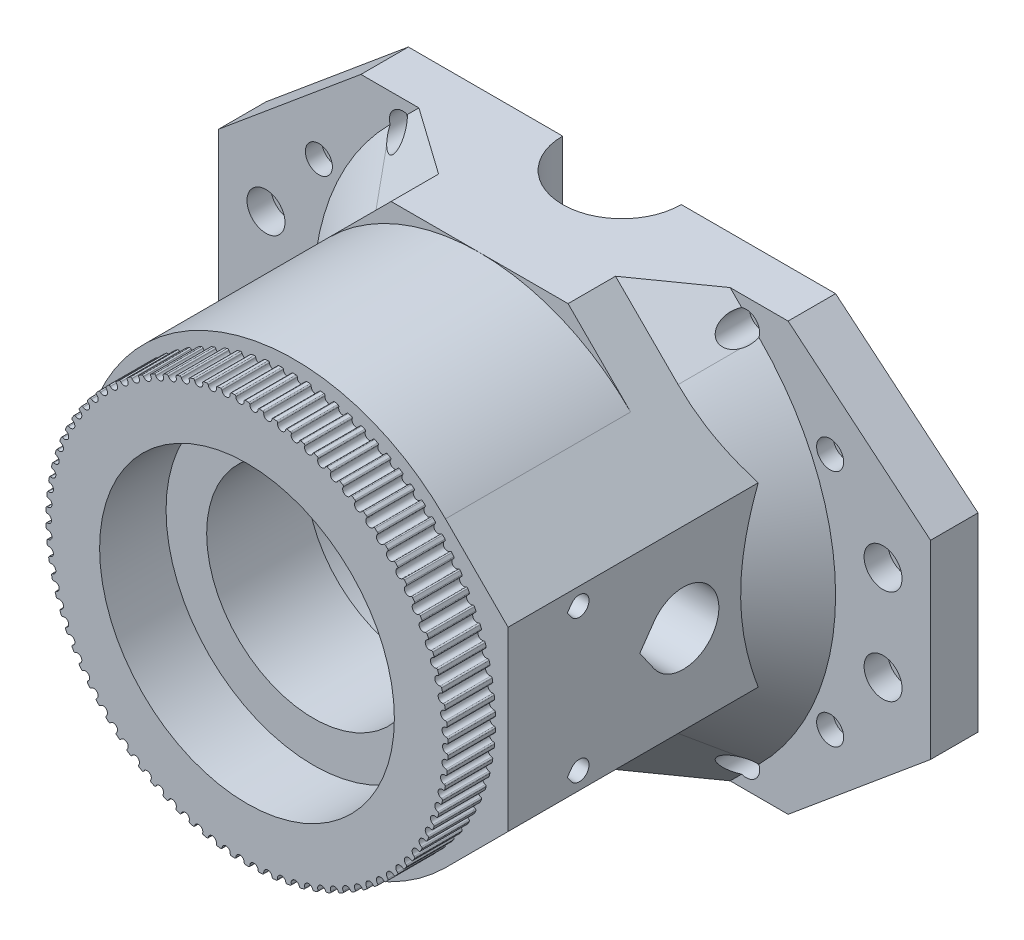
SolidWorks part; units mm, degrees
ref_plane "Front Plane" through (0, 0, 0) normal (1, 0, 0) x (0, 1, 0)
ref_plane "Top Plane" through (0, 0, 0) normal (0, 0, 1) x (0, 1, 0)
ref_plane "Right Plane" through (0, 0, 0) normal (0, 1, 0) x (-1, 0, 0)
sketch "Sketch1" plane through (0, 0, 0) normal (1, 0, 0) x (0, 1, 0)
  line L0 (-45, -80) -> (45, -80)
  line L1 (-31, 0) -> (31, 0)
  line L2 (-31, 0) -> (-31, -14)
  line L3 (-31, -14) -> (31, -14)
  line L4 (31, 0) -> (31, -14)
  line L5 (-31, 0) -> (31, -14) construction
  line L6 (-31, -14) -> (31, 0) construction
  line L7 (-31, -36) -> (31, -36)
  line L8 (-31, -36) -> (-31, -50)
  line L9 (-31, -50) -> (31, -50)
  line L10 (31, -36) -> (31, -50)
  line L11 (-31, -36) -> (31, -50) construction
  line L12 (-31, -50) -> (31, -36) construction
  line L13 (45, -80) -> (45, -1)
  line L14 (45, -1) -> (31, -1)
  line L15 (-31, -1) -> (-45, -1)
  line L16 (-45, -1) -> (-45, -80)
  point P0 (0, -7)
  point P5 (0, -43)
  point P16 (0, 0)
  dimension "D1" = 62
  dimension "D2" = 62
  dimension "D3" = 14
  dimension "D4" = 14
  dimension "D5" = 30
  dimension "D6" = 1
  dimension "D7" = 22
  dimension "D8" = 90
sketch "Sketch2" plane through (0, 0, 0) normal (0, 0, 1) x (0, 1, 0)
  line L0 (-45, 45) -> (-20, 75)
  line L1 (-20, 75) -> (20, 75)
  line L2 (45, 45) -> (-45, 45)
  line L3 (45, 45) -> (45, -45)
  line L4 (45, -45) -> (-45, -45)
  line L5 (-45, 45) -> (-45, -45)
  line L6 (45, 45) -> (-45, -45) construction
  line L7 (45, -45) -> (-45, 45) construction
  line L8 (20, 75) -> (45, 45)
  line L9 (-45, -45) -> (-20, -75)
  line L10 (-20, -75) -> (20, -75)
  line L11 (20, -75) -> (45, -45)
  line L12 (0, 75) -> (0, -75) construction
  line L13 (-45, -18.6396) -> (-18.6396, -45)
  line L14 (-18.6396, 45) -> (-45, 18.6396)
  line L15 (45, 18.6396) -> (18.6396, 45)
  line L16 (18.6396, -45) -> (45, -18.6396)
  circle A0 centre (0, 0) radius 45
  circle A1 centre (0, 0) radius 31.05
  circle A2 centre (0, 0) radius 22.5
  point P15 (0, 0)
  point P27 (0, 0)
  dimension "D1" = 90
  dimension "D2" = 62.1
  dimension "D3" = 45
  dimension "D4" = 150
  dimension "D5" = 40
  dimension "D6" = 4
  dimension "D7" = 45
extrude "Boss-Extrude1" add sketch "Sketch2" against normal up to vertex (80 mm away) from offset 11 contours A0 A1 | A1 A2 region at (-40.3987, 16.7337, 0) region at (0, -30.1718, 0) up to point (0, -45, -80) offset against normal yes
extrude "Boss-Extrude2" add sketch "Sketch2<3>" along normal blind 10 from surface contours A0 L5 L4 | A0 L2 L5 | A0 L4 L3 | A0 L3 L2 | L10 L11 L4 L9 | L8 L1 L0 L2 | A0 L13 L4 | A0 L5 L13 | A0 L4 | A0 L3 | A0 L2 L14 | A0 L14 L5 | A0 L3 L15 | A0 L15 L2 region at (-58.0769, 0, 0) region at (-36.2132, -36.2132, 0) region at (-42.2926, -17.5182, 0) region at (-17.5182, -42.2926, 0) region at (-42.2926, 17.5182, 0) region at (17.5182, -42.2926, 0) region at (-36.2132, 36.2132, 0) region at (-17.5182, 42.2926, 0) region at (36.2132, -36.2132, 0) region at (42.2926, -17.5182, 0) region at (17.5182, 42.2926, 0) region at (58.0769, 0, 0) region at (42.2926, 17.5182, 0) region at (36.2132, 36.2132, 0) starting at face at (45, 0, -80)
sketch "Sketch2<3>" plane through (0, 0, 0) normal (0, 0, 1) x (0, 1, 0) same geometry as "Sketch2"
extrude "Boss-Extrude4" add sketch "Sketch2<6>" along normal blind 20 from surface contours A0 L5 | A0 L5 L13 | A0 L16 L3 | A0 L3 L15 region at (-17.5182, -42.2926, 0) region at (17.5182, -42.2926, 0) region at (-17.5182, 42.2926, 0) region at (17.5182, 42.2926, 0) starting at face at (-47.5, 0, -70)
sketch "Sketch2<6>" plane through (0, 0, 0) normal (0, 0, 1) x (0, 1, 0) same geometry as "Sketch2"
sketch "Sketch5" plane through (0, -45, 0) normal (0, -1, 0) x (1, 0, 0)
  line L0 (-45, -80) -> (45, -80) construction
  circle A0 centre (0, -80) radius 12.5
  line M9 (-45, -80) -> (45, -80)
  dimension "D1" = 25
extrude "Cut-Extrude3" cut sketch "Sketch5" against normal through all contours A0 M9 region at (0, -45, -74.6948)
sketch "Sketch6" plane through (0, 0, -70) normal (0, 0, 1) x (1, 0, 0)
  line L0 (-65, 10) -> (-65, -10) construction
  line L1 (0, 0) -> (-99.7082, 0) construction
  line L2 (65, 10) -> (65, -10) construction
  line L3 (75, -20) -> (75, 20) construction
  line L4 (-75, -20) -> (-75, 20) construction
  circle A0 centre (65, 10) radius 4
  circle A1 centre (65, 10) radius 2.05
  circle A2 centre (-65, 10) radius 2.05
  circle A3 centre (-65, 10) radius 4
  circle A4 centre (-65, -10) radius 2.05
  circle A5 centre (-65, -10) radius 4
  circle A6 centre (65, -10) radius 2.05
  circle A7 centre (65, -10) radius 4
  point P3 (-65, 0)
  point P9 (65, 0)
  dimension "D4" = 8
  dimension "D5" = 4.1
  dimension "D1" = 20
  dimension "D2" = 10
  dimension "D3" = 10
  dimension "D6" = 2
  dimension "D7" = 2
extrude "Cut-Extrude4" cut sketch "Sketch6" against normal through all contours A1 | A4 | A2 | A6
extrude "Cut-Extrude5" cut sketch "Sketch6<4>" against normal blind 5
sketch "Sketch6<4>" plane through (0, 0, -70) normal (0, 0, 1) x (1, 0, 0) same geometry as "Sketch6"
extrude "Cut-Extrude1" cut sketch "Sketch2<4>" against normal blind 15 contours A1
sketch "Sketch2<4>" plane through (0, 0, 0) normal (0, 0, 1) x (0, 1, 0) same geometry as "Sketch2"
extrude "Cut-Extrude2" cut sketch "Sketch2<5>" against normal through all from vertex contours A1 starting at point (0, -31, -36)
sketch "Sketch2<5>" plane through (0, 0, 0) normal (0, 0, 1) x (0, 1, 0) same geometry as "Sketch2"
sketch "Sketch7" plane through (0, 0, -70) normal (0, 0, 1) x (1, 0, 0)
  line L0 (-75, 20) -> (75, 20) construction
  line L1 (-45, 45) -> (-18.6396, 45) construction
  line L2 (-45, 45) -> (0, 45) construction
  line L3 (-30, 45) -> (-60, 20) construction
  line L4 (-75, 20) -> (-45, 45) construction
  line L5 (0, 13.0372) -> (0, -13.0372) construction
  line L6 (-13.0372, 0) -> (13.0372, 0) construction
  line L7 (30, 45) -> (60, 20) construction
  line L8 (30, -45) -> (60, -20) construction
  line L9 (-30, -45) -> (-60, -20) construction
  circle A0 centre (-53.8542, 25.1215) radius 1.6
  circle A1 centre (-53.8542, 25.1215) radius 2.85
  circle A2 centre (-36.1458, 39.8785) radius 2.85
  circle A3 centre (-36.1458, 39.8785) radius 1.6
  circle A4 centre (36.1458, 39.8785) radius 1.6
  circle A5 centre (36.1458, 39.8785) radius 2.85
  circle A6 centre (53.8542, 25.1215) radius 2.85
  circle A7 centre (53.8542, 25.1215) radius 1.6
  circle A8 centre (53.8542, -25.1215) radius 1.6
  circle A9 centre (53.8542, -25.1215) radius 2.85
  circle A10 centre (36.1458, -39.8785) radius 2.85
  circle A11 centre (36.1458, -39.8785) radius 1.6
  circle A12 centre (-36.1458, -39.8785) radius 1.6
  circle A13 centre (-36.1458, -39.8785) radius 2.85
  circle A14 centre (-53.8542, -25.1215) radius 2.85
  circle A15 centre (-53.8542, -25.1215) radius 1.6
  circle A16 centre (-36.1458, -39.8785) radius 5.5
  circle A17 centre (36.1458, -39.8785) radius 5.5
  point P23 (0, 0)
  point P26 (0, 0)
  dimension "D2" = 5.7
  dimension "D3" = 3.2
  dimension "D6" = 3.2
  dimension "D7" = 5.7
  dimension "D8" = 11
  dimension "D9" = 11
  dimension "D1" = 15
  dimension "D4" = 8
  dimension "D5" = 8
extrude "Cut-Extrude6" cut sketch "Sketch7" against normal through all contours A15 | A0 | A3 | A4 | A7 | A8 | A11 | A12
extrude "Cut-Extrude7" cut sketch "Sketch7<3>" against normal blind 3.5 contours A14 | A1 | A2 | A5 | A6 | A9 | A10 | A13
sketch "Sketch7<3>" plane through (0, 0, -70) normal (0, 0, 1) x (1, 0, 0) same geometry as "Sketch7"
chamfer "Chamfer2" distance 10 angle 45 6 edges at (25.2297, -38.4099, -70) (25.2297, 38.4099, -70) (45, 0, -70) (-25.2297, 38.4099, -70) (-25.2297, -38.4099, -70) (-45, 0, -70)
extrude "Boss-Extrude6" add sketch "Sketch2<7>" against normal up to surface (70 mm away) from surface contours A0 L13 L4 | A0 L4 L16 region at (42.2926, -17.5182, 0) region at (42.2926, 17.5182, 0) up to face at (56.7042, -25.1215, -70) starting at face at (31.05, 0, -11)
sketch "Sketch2<7>" plane through (0, 0, 0) normal (0, 0, 1) x (0, 1, 0) same geometry as "Sketch2"
sketch "Sketch8" plane through (45, 0, 0) normal (1, 0, 0) x (0, 1, 0)
  line L0 (-15, -26) -> (-9.9, -26) construction
  line L1 (15, -26) -> (20.2, -26) construction
  line L2 (-15, -26) -> (-20.2, -26) construction
  line L3 (-9.9, -26) -> (15, -26) construction
  line L4 (-9.9, -26) -> (-9.9, -11) construction
  line L5 (18.6396, -11) -> (-18.6396, -11) construction
  line L6 (-20.2, -26) -> (-20.2, -11)
  line L7 (-31.8198, -11) -> (-18.6396, -11) construction
  line L8 (20.2, -26) -> (20.2, -11)
  line L9 (18.6396, -11) -> (31.8198, -11) construction
  line L10 (-14.0823, -24.6894) -> (-15, -24.0468)
  line L11 (-16.1758, -24.3207) -> (-15, -23.4974)
  line L12 (-15.9177, -24.6894) -> (-15, -24.0468)
  line L13 (-13.8242, -24.3207) -> (-15, -23.4974)
  line L14 (-15, -26) -> (-15, -23.4974) construction
  line L15 (16.1758, -24.3207) -> (15, -23.4974)
  line L16 (15, -26) -> (15, -23.4974) construction
  line L17 (14.0823, -24.6894) -> (15, -24.0468)
  line L18 (13.8242, -24.3207) -> (15, -23.4974)
  line L19 (15.9177, -24.6894) -> (15, -24.0468)
  line L20 (-20.2, -11) -> (20.2, -11)
  line L21 (-20.2, -26) -> (-20.2, -32.9)
  line L22 (20.2, -26) -> (20.2, -32.9)
  line L23 (-20.2, -32.9) -> (20.2, -32.9)
  line L24 (0, -47.9) -> (0, -38.7442) construction
  line L25 (-4.3018, -41.7564) -> (0, -38.7442)
  line L26 (4.3018, -41.7564) -> (0, -38.7442)
  arc A0 (-16.1758, -24.3207) -> (-13.8242, -24.3207) centre (-15, -26) ccw
  arc A1 (-15.9177, -24.6894) -> (-14.0823, -24.6894) centre (-15, -26) ccw
  arc A2 (14.0823, -24.6894) -> (15.9177, -24.6894) centre (15, -26) ccw
  arc A3 (13.8242, -24.3207) -> (16.1758, -24.3207) centre (15, -26) ccw
  arc A4 (-4.3018, -41.7564) -> (4.3018, -41.7564) centre (0, -47.9) ccw
  point P29 (0, -11)
  dimension "D6" = 3.2
  dimension "D7" = 4.1
  dimension "D10" = 3.2
  dimension "D11" = 4.1
  dimension "D15" = 15
  dimension "D1" = 15
  dimension "D2" = 24.9
  dimension "D3" = 5.2
  dimension "D4" = 5.1
  dimension "D5" = 5.2
  dimension "D8" = 55
  dimension "D9" = 55
  dimension "D12" = 55
  dimension "D13" = 55
  dimension "D14" = 6.9
  dimension "D16" = 15
  dimension "D17" = 55
sketch "Sketch3" plane through (0, 0, -11) normal (0, 0, 1) x (1, 0, 0)
  line L0 (0, 0) -> (0, 42.3568)
  line L1 (0, 0) -> (1.4374, 41.1617) construction
  line L2 (0, 0) -> (2.9547, 42.2537)
  line L3 (1.4374, 41.1617) -> (1.4678, 42.0312) construction
  arc A0 (0.6589, 42.3517) -> (2.297, 42.2945) centre (1.4678, 42.0312) ccw
  arc A1 (0, 42.3568) -> (0.6589, 42.3517) centre (0, 0) cw
  arc A2 (2.297, 42.2945) -> (2.9547, 42.2537) centre (0, 0) cw
  arc A3 (0, 31.05) -> (2.1659, 30.9744) centre (0, 0) cw
  circle A4 centre (0, 0) radius 31.05 construction
  circle M5 centre (0, 0) radius 31.05
  dimension "D1" = 42.3568
  dimension "D2" = 2
  dimension "D3" = 2
  dimension "D4" = 42.3568
  dimension "D5" = 41.1868
  dimension "D6" = 0.87
extrude "Boss-Extrude3" add sketch "Sketch3" along normal blind 10 contours A2 A0 A1 L0 L2 M5 region at (1.2803, 36.6619, -11)
fillet "Fillet1" radius 0.26 2 edges at (2.297, 42.2945, -6) (0.6589, 42.3517, -6)
pattern_circular "CirPattern1" count 90 over 360 about axis through (0, 0, -80) along (0, 0, 1) of "Fillet1", "Boss-Extrude3" reverse direction yes
extrude "Cut-Extrude9" cut sketch "Sketch8" against normal blind 7 contours A0 L13 L11 | A3 L15 L18
extrude "Cut-Extrude10" cut sketch "Sketch8<3>" against normal blind 3 from surface contours A1 L10 L12 | A2 L19 L17 starting at face at (38, -15, -25.2894)
sketch "Sketch8<3>" plane through (45, 0, 0) normal (1, 0, 0) x (0, 1, 0) same geometry as "Sketch8"
extrude "Cut-Extrude11" cut sketch "Sketch8<4>" against normal blind 45 contours A4 L26 L25
sketch "Sketch8<4>" plane through (45, 0, 0) normal (1, 0, 0) x (0, 1, 0) same geometry as "Sketch8"
equation "\"D1@Sketch3\"=3 * 90 / PI / 2-0.615"
equation "\"D3@Sketch3\"=\"D2@Sketch3\""
equation "\"D4@Sketch3\"=\"D1@Sketch3\""
equation "\"D5@Sketch3\"=\"D1@Sketch3\"-1.17"
